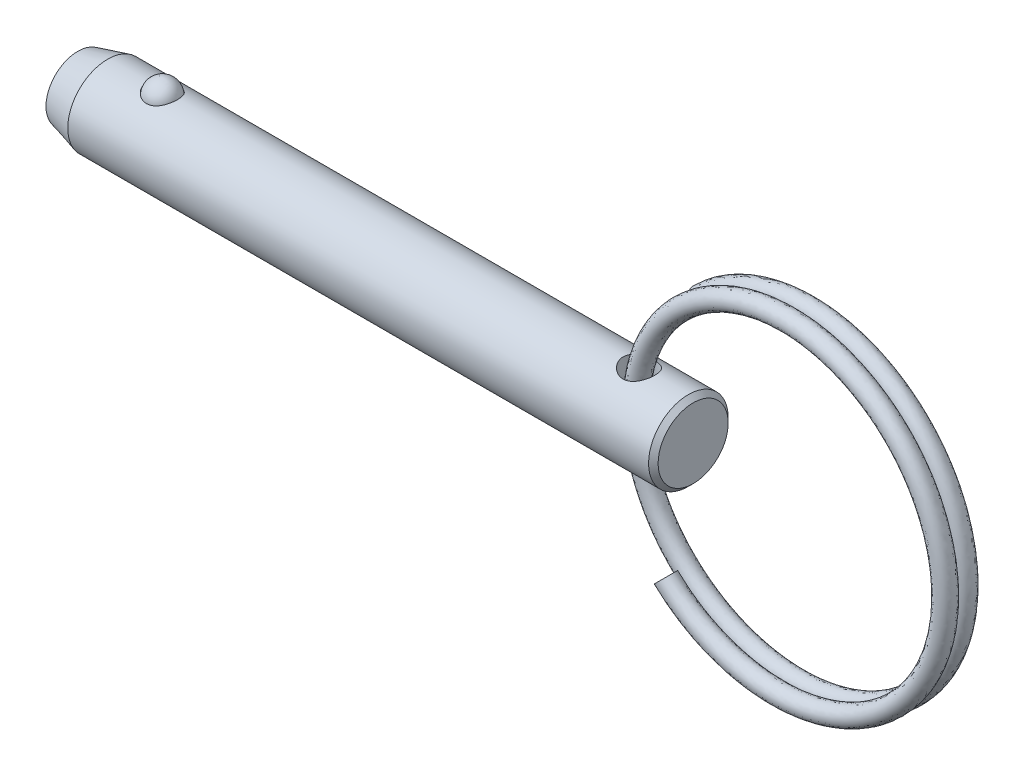
SolidWorks part; units mm, degrees
ref_plane "Front" through (0, 0, 0) normal (0, 0, 1) x (1, 0, 0)
ref_plane "Top" through (0, 0, 0) normal (0, 1, 0) x (1, 0, 0)
ref_plane "Right" through (0, 0, 0) normal (1, 0, 0) x (0, 0, -1)
sketch "Sketch1" plane through (0, 0, 0) normal (0, 0, 1) x (1, 0, 0)
  line L0 (24.5364, 2.794) -> (24.1554, 3.175)
  line L1 (24.1554, 3.175) -> (24.5364, 3.175) construction
  line L4 (24.5364, 2.794) -> (24.5364, 0)
  line L5 (24.5364, 3.175) -> (24.5364, 2.794) construction
  line L16 (24.1554, 3.175) -> (-22.1665, 3.175)
  line L17 (-24.5364, 3.175) -> (-24.5364, 2.54) construction
  line L19 (-22.1665, 3.175) -> (-24.5364, 3.175) construction
  line L22 (-24.5364, -3.175) -> (-22.1665, -3.175) construction
  line L23 (-17.8019, 2.8575) -> (-17.8019, -2.8575) construction
  line L24 (-24.5364, 0) -> (24.5364, 0)
  line L27 (24.5364, 0) -> (27.3304, 0) construction
  line L29 (-24.5364, 0) -> (-24.5364, -2.54) construction
  line L36 (18.9484, 0) -> (18.9484, 3.175) construction
  line L37 (-24.5364, 2.54) -> (-24.5364, 0)
  line L38 (-22.1665, -3.175) -> (24.5364, -3.175) construction
  line L39 (-24.5364, -2.54) -> (-24.5364, -3.175) construction
  line L40 (-22.1665, 3.175) -> (-24.5364, 2.54)
  line L42 (-22.1665, -3.175) -> (-24.5364, -2.54) construction
  line L43 (-22.1665, 3.175) -> (-22.1665, -3.175) construction
  circle A2 centre (-17.8019, 2.8575) radius 1.2319 construction
  point P35 (-16.6116, 3.175)
  dimension "D2" = 5.715
  dimension "D11" = 0.9144
  dimension "A" = 6.35
  dimension "D" = 5.588
  dimension "E" = 7.2644
  dimension "D3" = 0.381
  dimension "Useable Length" = 35.56
  dimension "D12" = 5.08
  dimension "C" = 7.9248
  dimension "A1" = 15
revolve "Revolve1" add sketch "Sketch1" angle 360 about L27
sketch "Sketch2" plane through (0, 0, 0) normal (0, 0, 1) x (1, 0, 0)
  line L0 (-16.5446, 2.8575) -> (-19.0592, 2.8575)
  line L1 (-17.8019, 4.0894) -> (-17.8019, 4.1148) construction
  line L2 (-16.5446, 2.8575) -> (-14.03, 2.8575) construction
  circle A0 centre (-17.8019, 2.8575) radius 1.2319 construction
  circle A1 centre (-17.8019, 2.8575) radius 1.2319 construction
  arc A2 (-19.0592, 2.8575) -> (-16.5446, 2.8575) centre (-17.8019, 2.8575) cw
  dimension "D1" = 0.0254
revolve "Cut-Revolve1" cut sketch "Sketch2" angle 360 about L2
sketch "Sketch3" plane through (0, 0, 0) normal (0, 0, 1) x (1, 0, 0)
  line L0 (-16.57, 2.8575) -> (-19.0338, 2.8575)
  line L1 (-16.57, 2.8575) -> (-14.1062, 2.8575) construction
  circle A0 centre (-17.8019, 2.8575) radius 1.2319 construction
  arc A1 (-16.57, 2.8575) -> (-19.0338, 2.8575) centre (-17.8019, 2.8575) ccw
revolve "Revolve2" add sketch "Sketch3" angle 360 about L1
sketch "Sketch4" plane through (0, 0, 0) normal (0, 0, 1) x (1, 0, 0)
  line L1 (20.2184, -3.175) -> (21.4884, -3.175)
  line L2 (20.2184, -3.175) -> (20.2184, 3.175)
  line L3 (20.2184, 3.175) -> (21.4884, 3.175)
  line L4 (21.4884, -3.175) -> (21.4884, 3.175)
  line L5 (20.2184, -3.175) -> (20.2184, -4.445) construction
  line L6 (21.4884, 3.175) -> (24.5364, 3.175) construction
  line L8 (18.9484, -3.175) -> (18.9484, 3.175) construction
  line L9 (18.9484, 0) -> (20.2184, 0) construction
  line L11 (20.2184, 0) -> (21.4884, 0) construction
  line L12 (24.1554, 3.175) -> (-22.1665, 3.175) construction
  line L14 (-22.1665, -3.175) -> (24.5364, -3.175) construction
  dimension "D1" = 2.54
revolve "Cut-Revolve2" cut sketch "Sketch4" angle 360 about L2
sketch "Sketch5" plane through (0, 0, 0) normal (0, 0, 1) x (1, 0, 0)
  line L0 (0, 0) -> (19.2414, 0) construction
  line L1 (19.2414, 0) -> (19.2414, 3.175) construction
  line L2 (24.1554, 3.175) -> (-22.1665, 3.175) construction
  line L3 (32.7034, 0) -> (46.1654, 0) construction
  line L4 (21.4884, 3.175) -> (21.1954, 3.175) construction
  line L5 (20.2184, 3.175) -> (21.4884, 3.175) construction
  line L6 (19.6212, 3.175) -> (19.6212, -3.175) construction
  line L7 (19.2414, 3.175) -> (18.9484, 3.175) construction
  line L8 (20.2184, -3.175) -> (21.4884, -3.175) construction
  line L9 (19.6212, -3.175) -> (21.4884, -3.175) construction
  line L10 (19.2414, 0) -> (32.7034, 0) construction
  line L12 (21.1954, 3.175) -> (19.6212, 3.175) construction
  line L13 (32.7034, 11.938) -> (32.7034, 13.462) construction
  circle A0 centre (32.7034, 0) radius 13.462
  circle A1 centre (32.7034, 0) radius 11.938 construction
  circle A2 centre (32.7034, 0) radius 12.7 construction
  point P26 (32.7034, 12.7)
  dimension "R Ring Dia" = 25.4
  dimension "Ring OD" = 1.524
curve "Helix/Spiral1" pitch 1.5494 height 1.3557 radius 13.462 left hand yes centre (32.7034, 0, 0) axis (0, 0, -1) start towards (1, 0, 0)
sketch "Sketch6" plane through (114.0038, 0, 0) normal (0, 1, 0) x (0, 0, -1)
  line L0 (0, 93.2384) -> (0, 94.0004) construction
  line L1 (0, 94.0004) -> (0, 94.7624) construction
  circle A0 centre (0, 94.0004) radius 0.762
  dimension "D1" = 1.524
sketch "Sketch7" plane through (0, 0, 0) normal (0, 0, 1) x (1, 0, 0)
  circle A0 centre (32.7034, 0) radius 13.462 construction
  circle A1 centre (32.7034, 0) radius 13.462
curve "Helix/Spiral2" pitch 1.5494 height 1.3557 radius 13.462 left hand yes centre (32.7034, 0, 0) axis (0, 0, 1) start towards (1, 0, 0)
sweep "Sweep1" add profiles "Sketch6" path "Helix/Spiral1"
sweep "Sweep2" add profiles "Sketch6<2>" path "Helix/Spiral2"
sketch "Sketch6<2>" plane through (114.0038, 0, 0) normal (0, 1, 0) x (0, 0, -1) same geometry as "Sketch6"
equation "\"D12@Sketch1\"=\"A@Sketch1\" * 0.80"
equation "\"D2@Sketch1\"=\"A@Sketch1\" * 0.9"
equation "\"D1@Sketch4\" = \"A@Sketch1\" / 2.5"
equation "\"Ring OD@Sketch5\" = \"R Ring Dia@Sketch5\" * 0.06"
equation "\"D4@Helix/Spiral1\"=\"Ring OD@Sketch5\" + 0.001"
equation "\"D1@Sketch6\"=\"Ring OD@Sketch5\""
equation "\"D4@Helix/Spiral2\" = \"D4@Helix/Spiral1\""
equation "\"D5@Helix/Spiral2\" = \"D5@Helix/Spiral1\""
